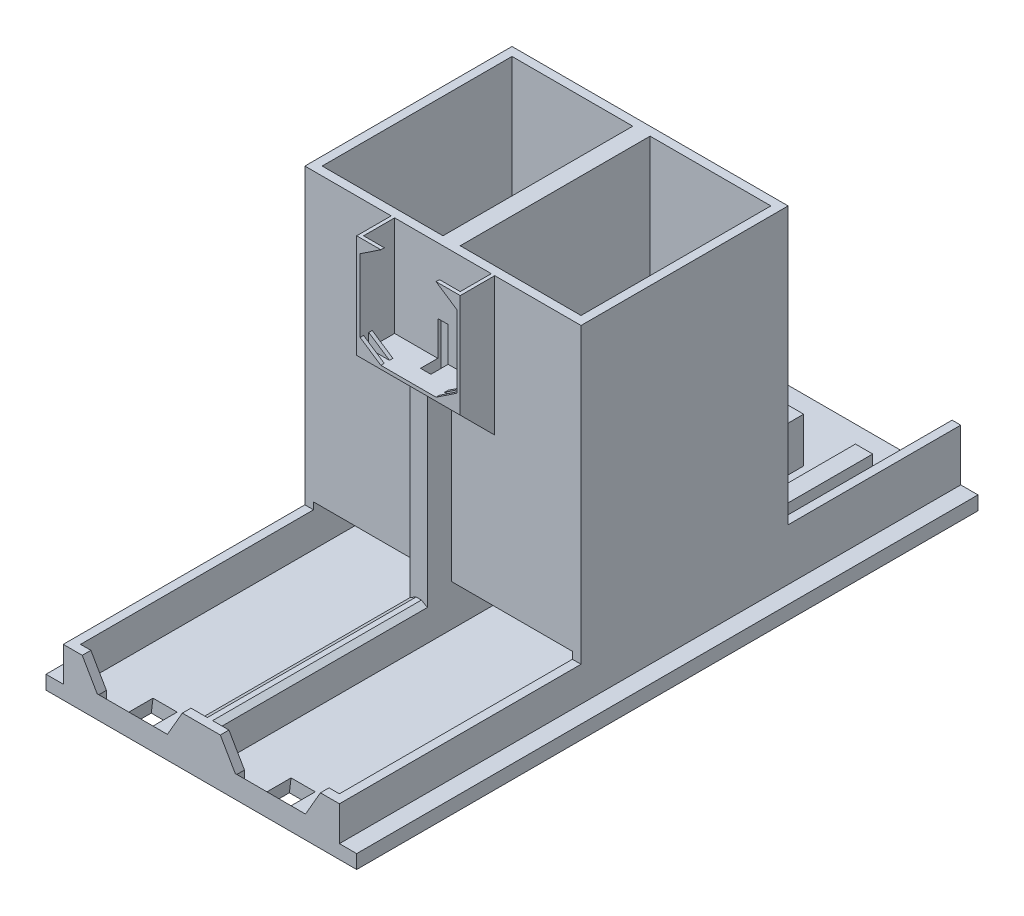
SolidWorks part; units mm, degrees
ref_plane "Front Plane" through (0, 0, 0) normal (0, 0, 1) x (1, 0, 0)
ref_plane "Top Plane" through (0, 0, 0) normal (0, 1, 0) x (1, 0, 0)
ref_plane "Right Plane" through (0, 0, 0) normal (1, 0, 0) x (0, 0, -1)
sketch "Sketch1" plane through (0, 0, 0) normal (0, 1, 0) x (1, 0, 0)
  line L1 (0, 0) -> (80, 0)
  line L2 (0, 0) -> (0, 60)
  line L3 (0, 60) -> (80, 60)
  line L4 (80, 0) -> (80, 60)
sketch "Sketch2" plane through (0, 0, 0) normal (0, 1, 0) x (1, 0, 0)
  line L1 (2.5, 57.5) -> (37.5, 57.5)
  line L2 (2.5, 57.5) -> (2.5, 2.5)
  line L3 (2.5, 2.5) -> (37.5, 2.5)
  line L4 (37.5, 57.5) -> (37.5, 2.5)
  line L5 (42.5, 57.5) -> (77.5, 57.5)
  line L6 (42.5, 57.5) -> (42.5, 2.5)
  line L7 (42.5, 2.5) -> (77.5, 2.5)
  line L8 (77.5, 57.5) -> (77.5, 2.5)
  dimension "D1" = 35
extrude "Boss-Extrude1" add sketch "Sketch1" along normal blind 100
extrude "Cut-Extrude1" cut sketch "Sketch2" along normal blind 95 from offset 5
sketch "Sketch3" plane through (0, 0, 0) normal (0, 0, 1) x (1, 0, 0)
  line L0 (80, 100) -> (80, 0) construction
  line L1 (0, 0) -> (80, 0)
  line L2 (0, 0) -> (0, 5)
  line L3 (0, 5) -> (80, 5)
  line L4 (80, 0) -> (80, 5)
extrude "Boss-Extrude2" add sketch "Sketch3" along normal blind 70
sketch "Sketch4" plane through (0, 5, 0) normal (0, 1, 0) x (1, 0, 0)
  line L0 (80, 0) -> (77.5, 0)
  line L5 (0, 0) -> (0, -70)
  line L18 (0, -70) -> (80, -70)
  line L19 (80, -70) -> (80, 0)
  line L20 (80, 0) -> (0, 0) construction
  line L21 (77.5, 0) -> (77.5, -67.5)
  line L22 (77.5, -67.5) -> (42.5, -67.5)
  line L23 (42.5, -67.5) -> (42.5, 0)
  line L24 (0, 0) -> (80, 0) construction
  line L25 (42.5, 0) -> (37.5, 0)
  line L26 (37.5, 0) -> (37.5, -67.5)
  line L27 (37.5, -67.5) -> (2.5, -67.5)
  line L28 (2.5, -67.5) -> (2.5, 0)
  line L29 (2.5, 0) -> (0, 0)
extrude "Boss-Extrude3" add sketch "Sketch4" along normal blind 10
sketch "Sketch5" plane through (0, 15, 0) normal (0, 1, 0) x (1, 0, 0)
  line L0 (37.5, -67.5) -> (2.5, -67.5) construction
  line L1 (10, -67.5) -> (30, -67.5)
  line L2 (10, -67.5) -> (10, -70)
  line L3 (10, -70) -> (30, -70)
  line L4 (30, -67.5) -> (30, -70)
  line L5 (0, -70) -> (80, -70) construction
  line L6 (77.5, -67.5) -> (42.5, -67.5) construction
  line L7 (70, -67.5) -> (50, -67.5)
  line L8 (70, -67.5) -> (70, -70)
  line L9 (70, -70) -> (50, -70)
  line L10 (50, -67.5) -> (50, -70)
  line L12 (37.5, 0) -> (37.5, -67.5) construction
  line L13 (42.5, -67.5) -> (42.5, 0) construction
  line L14 (77.5, 0) -> (77.5, -67.5) construction
  line L15 (2.5, -67.5) -> (2.5, 0) construction
  dimension "D1" = 7.5
  dimension "D2" = 7.5
  dimension "D3" = 7.5
  dimension "D4" = 7.5
extrude "Cut-Extrude2" cut sketch "Sketch5" against normal blind 7.5
sketch "Sketch6" plane through (0, 0, 0) normal (0, 0, 1) x (1, 0, 0)
  line L1 (2.5, 17) -> (37.5, 17)
  line L2 (2.5, 17) -> (2.5, 5)
  line L3 (2.5, 5) -> (37.5, 5)
  line L4 (37.5, 17) -> (37.5, 5)
  line L5 (42.5, 5) -> (77.5, 5)
  line L6 (42.5, 5) -> (42.5, 17)
  line L7 (42.5, 17) -> (77.5, 17)
  line L8 (77.5, 5) -> (77.5, 17)
extrude "Cut-Extrude4" cut sketch "Sketch6" against normal blind 57.5
sketch "Sketch7" plane through (0, 0, -60) normal (0, 0, -1) x (-1, 0, 0)
  circle A0 centre (-20, 11.5) radius 4
  circle A1 centre (-60, 11.5) radius 4
extrude "Cut-Extrude6" cut sketch "Sketch7" against normal up to next
sketch "Sketch9" plane through (0, 0, 0) normal (0, 1, 0) x (1, 0, 0)
  line L1 (0, 60) -> (80, 60)
  line L2 (0, 60) -> (0, 110)
  line L3 (0, 110) -> (80, 110)
  line L4 (80, 60) -> (80, 110)
extrude "Boss-Extrude4" add sketch "Sketch9" along normal blind 5
sketch "Sketch13" plane through (0, 5, 0) normal (0, 1, 0) x (1, 0, 0)
  line L0 (37.5, -67.5) -> (2.5, -67.5) construction
  line L1 (16, -67.5) -> (24, -67.5)
  line L2 (16, -67.5) -> (16, -60.5)
  line L3 (16, -60.5) -> (24, -60.5)
  line L4 (24, -67.5) -> (24, -60.5)
  line L10 (2.5, 57.5) -> (2.5, -67.5) construction
  line L11 (37.5, -67.5) -> (37.5, 57.5) construction
  line L12 (40, -70) -> (40, -52.9537) construction
  line L13 (30, -70) -> (50, -70) construction
  line L15 (56, -67.5) -> (56, -60.5)
  line L16 (64, -60.5) -> (56, -60.5)
  line L17 (64, -67.5) -> (64, -60.5)
  line L18 (64, -67.5) -> (56, -67.5)
  point P12 (16, -64)
  dimension "D1" = 13.5
  dimension "D2" = 13.5
  dimension "D3" = 7
extrude "Cut-Extrude8 (Button Holes)" cut sketch "Sketch13" against normal through all
sketch "Sketch14" plane through (0, 0, 0) normal (0, 0, 1) x (1, 0, 0)
  line L0 (0, 100) -> (80, 100) construction
  line L1 (25, 100) -> (26, 100)
  line L2 (25, 100) -> (25, 70)
  line L3 (25, 70) -> (26, 70)
  line L4 (26, 100) -> (26, 71)
  line L6 (54, 100) -> (55, 100)
  line L7 (54, 100) -> (54, 71)
  line L8 (54, 70) -> (55, 70)
  line L9 (55, 100) -> (55, 70)
  line L10 (26, 70) -> (54, 70)
  line L12 (26, 71) -> (54, 71)
  dimension "D1" = 30
  dimension "D2" = 1
  dimension "D3" = 1
extrude "Boss-Extrude5 (OLED Mount)" add sketch "Sketch14" along normal blind 10
sketch "Sketch15" plane through (0, 0, 10) normal (0, 0, 1) x (1, 0, 0)
  line L6 (40, 70) -> (40, 81.9127) construction
  line L7 (25, 70) -> (55, 70) construction
  line L8 (26, 71) -> (26, 100) construction
  line L14 (26, 71) -> (32, 71)
  line L15 (54, 71) -> (26, 71) construction
  line L16 (32, 71) -> (26, 75)
  line L17 (26, 75) -> (26, 71)
  line L18 (54, 75) -> (54, 71)
  line L19 (48, 71) -> (54, 75)
  line L20 (54, 71) -> (48, 71)
  dimension "D1" = 6
  dimension "D2" = 4
  dimension "D3" = 14
sketch "Sketch17" plane through (0, 0, 10) normal (0, 0, 1) x (1, 0, 0)
  line L0 (40, 100) -> (40, 89.7245) construction
  line L9 (26, 100) -> (54, 100) construction
  line L10 (54, 96) -> (54, 100)
  line L11 (48, 100) -> (54, 96)
  line L12 (26, 100) -> (32, 100)
  line L13 (32, 100) -> (26, 96)
  line L14 (26, 71) -> (26, 100) construction
  line L15 (26, 96) -> (26, 100)
  line L16 (54, 100) -> (48, 100)
  dimension "D1" = 6
  dimension "D2" = 4
extrude "Boss-Extrude6 (OLED Mount)" add sketch "Sketch15" against normal blind 1
extrude "Boss-Extrude7 (OLED Mount)" add sketch "Sketch15<2>" against normal blind 1 from offset 2.5 offset against normal yes
sketch "Sketch15<2>" plane through (0, 0, 10) normal (0, 0, 1) x (1, 0, 0) same geometry as "Sketch15"
extrude "Boss-Extrude8 (OLED Mount)" add sketch "Sketch17" against normal blind 1
sketch "Sketch32" plane through (25, 0, 0) normal (-1, 0, 0) x (0, 0, 1)
  line L0 (0, 70) -> (10, 70)
  line L1 (10, 70) -> (0, 60)
  line L3 (0, 60) -> (0, 70)
  line L4 (0, 15) -> (0, 17) construction
extrude "Boss-Extrude13 OLED Mount Support)" add sketch "Sketch32" against normal blind 30
sketch "Sketch18" plane through (0, 71, 0) normal (0, 1, 0) x (1, 0, 0)
  line L0 (26, 0) -> (54, 0) construction
  line L5 (42.5, 57.5) -> (42.5, -67.5) construction
  line L8 (38.5, 1) -> (41.5, 1)
  line L9 (38.5, 1) -> (38.5, -5)
  line L10 (38.5, -5) -> (41.5, -5)
  line L11 (41.5, 1) -> (41.5, -5)
  line L12 (37.5, -67.5) -> (37.5, 57.5) construction
  dimension "D1" = 1
  dimension "D2" = 1
  dimension "D3" = 1
  dimension "D4" = 5
extrude "Cut-Extrude9 (OLED Cable)" cut sketch "Sketch18" against normal through all and the other way blind 10
sketch "Sketch31" plane through (0, 15, 0) normal (0, 1, 0) x (1, 0, 0)
  line L0 (37.5, 0) -> (38.5, 0)
  line L1 (38.5, 0) -> (38.5, -5)
  line L2 (38.5, -5) -> (41.5, -5)
  line L3 (41.5, -5) -> (41.5, 0)
  line L4 (41.5, 0) -> (42.5, 0)
  line L5 (42.5, 0) -> (42.5, -7)
  line L6 (42.5, -7) -> (37.5, -7)
  line L7 (37.5, 0) -> (37.5, -67.5) construction
  line L8 (37.5, -7) -> (37.5, 0)
  dimension "D1" = 2
extrude "Boss-Extrude12 (OLED Cable Guide)" add sketch "Sketch31" along normal up to next
sketch "Sketch20" plane through (0, 5, 0) normal (0, 1, 0) x (1, 0, 0)
  line L0 (0, 60) -> (80, 60) construction
  line L1 (62.5, 60) -> (57.5, 60)
  line L2 (62.5, 60) -> (62.5, 65)
  line L3 (62.5, 65) -> (57.5, 65)
  line L4 (57.5, 60) -> (57.5, 65)
  line L5 (80, 60) -> (80, 110) construction
  line L7 (40, 110) -> (40, 60) construction
  line L8 (80, 110) -> (0, 110) construction
  line L9 (17.5, 65) -> (22.5, 65)
  line L10 (22.5, 60) -> (22.5, 65)
  line L11 (17.5, 60) -> (22.5, 60)
  line L12 (17.5, 60) -> (17.5, 65)
  point P8 (60, 60)
  dimension "D1" = 5
  dimension "D2" = 17.5
  dimension "D3" = 5
  dimension "D4" = 40
extrude "Cut-Extrude10 (Solenoid Wire Hole)" cut sketch "Sketch20" against normal through all
sketch "Sketch21" plane through (0, 5, 0) normal (0, 1, 0) x (1, 0, 0)
  line L0 (62.5, 60) -> (80, 60) construction
  line L1 (67.5, 60) -> (72.5, 60)
  line L2 (67.5, 60) -> (67.5, 92)
  line L3 (67.5, 92) -> (72.5, 92)
  line L4 (72.5, 60) -> (72.5, 92)
  line L7 (80, 110) -> (0, 110) construction
  line L9 (40, 60) -> (40, 110) construction
  line L10 (22.5, 60) -> (57.5, 60) construction
  line L11 (0, 110) -> (0, 60) construction
  line L12 (60, 110) -> (60, 60) construction
  line L13 (80, 60) -> (80, 110) construction
  line L15 (47.5, 60) -> (47.5, 92)
  line L16 (52.5, 92) -> (47.5, 92)
  line L17 (52.5, 60) -> (52.5, 92)
  line L18 (52.5, 60) -> (47.5, 60)
  line L19 (27.5, 60) -> (32.5, 60)
  line L20 (27.5, 60) -> (27.5, 92)
  line L21 (32.5, 60) -> (32.5, 92)
  line L22 (27.5, 92) -> (32.5, 92)
  line L23 (7.5, 60) -> (7.5, 92)
  line L24 (12.5, 92) -> (7.5, 92)
  line L25 (12.5, 60) -> (12.5, 92)
  line L26 (12.5, 60) -> (7.5, 60)
  dimension "D1" = 5
  dimension "D2" = 40
  dimension "D3" = 20
  dimension "D4" = 7.5
  dimension "D5" = 32
extrude "Boss-Extrude9 (Solenoid Side Support)" add sketch "Sketch21" along normal blind 13
sketch "Sketch27" plane through (0, 5, 0) normal (0, 1, 0) x (1, 0, 0)
  line L0 (80, 110) -> (0, 110) construction
  line L1 (80, 60) -> (77.5, 60)
  line L2 (80, 60) -> (80, 110)
  line L3 (80, 110) -> (77.5, 110)
  line L4 (77.5, 60) -> (77.5, 110)
  line L6 (0, 60) -> (2.5, 60)
  line L7 (0, 60) -> (0, 110)
  line L8 (0, 110) -> (2.5, 110)
  line L9 (2.5, 60) -> (2.5, 110)
  dimension "D1" = 2.5
  dimension "D2" = 2.5
extrude "Boss-Extrude13 (Solenoid Section Walls)" add sketch "Sketch27" along normal blind 15
sketch "Sketch29" plane through (80, 0, 0) normal (1, 0, 0) x (0, 0, -1)
  line L0 (-70, 0) -> (-70, 15) construction
  line L1 (-70, 5) -> (110, 5)
  line L2 (-70, 5) -> (-70, 0)
  line L3 (-70, 0) -> (110, 0)
  line L4 (110, 5) -> (110, 0)
  line L5 (110, 20) -> (110, 0) construction
  line L6 (-70, 0) -> (110, 0) construction
  dimension "D1" = 5
extrude "Boss-Extrude9 (Guide)" add sketch "Sketch29" along normal blind 5
extrude "Boss-Extrude10 (Guide)" add sketch "Sketch29<3>" against normal blind 5 from offset 80 offset against normal yes
sketch "Sketch29<3>" plane through (80, 0, 0) normal (1, 0, 0) x (0, 0, -1) same geometry as "Sketch29"
sketch "Sketch33" plane through (0, 0, 0) normal (0, -1, 0) x (1, 0, 0)
  line L1 (-5, 70) -> (85, 70)
  line L2 (-5, 70) -> (-5, -110)
  line L3 (-5, -110) -> (85, -110)
  line L4 (85, 70) -> (85, -110)
extrude "Cut-Extrude7 (Slim Base)" cut sketch "Sketch33" against normal blind 1
sketch "Sketch34" plane through (0, 0, 60.5) normal (0, 0, 1) x (1, 0, 0)
  line L0 (16, 5) -> (16.5, 5)
  line L1 (24, 5) -> (16, 5) construction
  line L2 (16.5, 5) -> (16, 1)
  line L3 (16, 1) -> (16, 5)
  line L4 (24, 5) -> (24, 1)
  line L5 (24, 1) -> (23.5, 5)
  line L6 (23.5, 5) -> (24, 5)
  line L8 (40, 1) -> (40, 5.9951) construction
  line L9 (85, 1) -> (-5, 1) construction
  line L10 (56.5, 5) -> (56, 5)
  line L11 (56, 1) -> (56.5, 5)
  line L12 (56, 5) -> (56, 1)
  line L13 (64, 1) -> (64, 5)
  line L14 (63.5, 5) -> (64, 1)
  line L15 (64, 5) -> (63.5, 5)
  dimension "D1" = 0.5
  dimension "D2" = 0.5
extrude "Boss-Extrude5" add sketch "Sketch34" along normal up to next
chamfer "Chamfer3 (Thumb)" distance 2.5 angle 45 2 edges at (20, 7.5, 67.5) (60, 7.5, 67.5)
chamfer "Chamfer5 (Thumb)" distance 4.5 angle 60 4 edges at (70, 15, 68.75) (50, 15, 68.75) (30, 15, 68.75) (10, 15, 68.75) first distance on face at (75.8333, 15, 45.8333) first distance on face at (40, 15, 53) first distance on face at (4.1667, 15, 45.8333)
chamfer "Chamfer6" distance 1 angle 60 2 edges at (42.5, 15, 37.25) (37.5, 15, 37.25) first distance on face at (42.5, 40.1, 2.9) first distance on face at (37.5, 40.1, 2.9)
